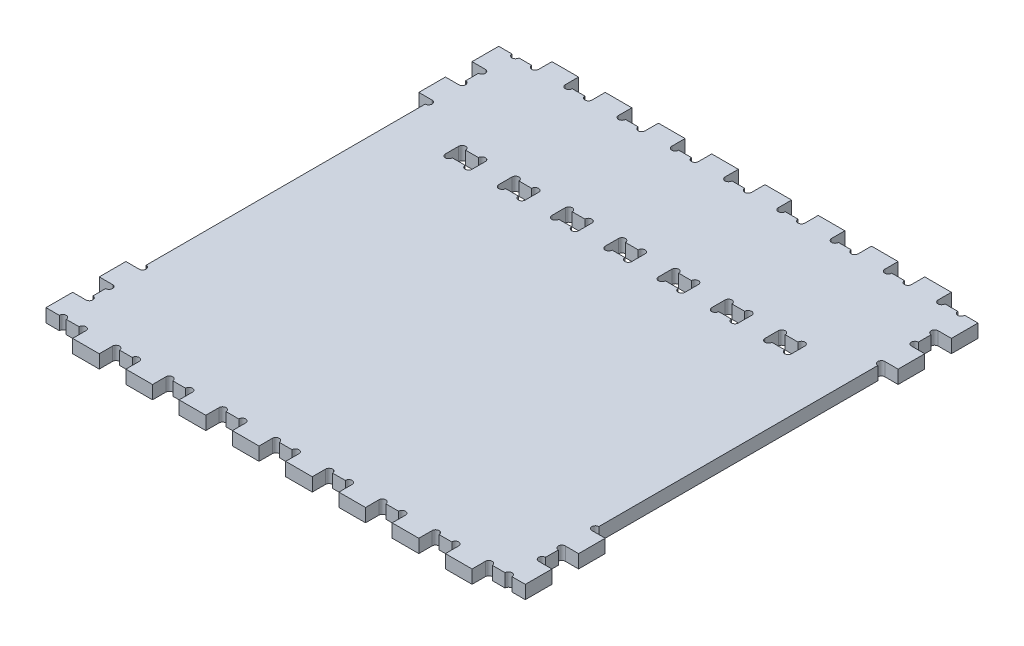
SolidWorks part; units mm, degrees
ref_plane "Front Plane" through (0, 0, 0) normal (0, 0, 1) x (1, 0, 0)
ref_plane "Top Plane" through (0, 0, 0) normal (0, 1, 0) x (1, 0, 0)
ref_plane "Right Plane" through (0, 0, 0) normal (1, 0, 0) x (0, 0, -1)
sketch "Sketch1" plane through (0, 0, 0) normal (0, 1, 0) x (1, 0, 0)
  line L1 (228.6, -228.6) -> (-228.6, -228.6)
  line L2 (228.6, -228.6) -> (228.6, 228.6)
  line L3 (228.6, 228.6) -> (-228.6, 228.6)
  line L4 (-228.6, -228.6) -> (-228.6, 228.6)
  line L5 (228.6, -228.6) -> (-228.6, 228.6) construction
  line L6 (228.6, 228.6) -> (-228.6, -228.6) construction
  point P0 (0, 0)
  dimension "D1" = 457.2
  dimension "D2" = 457.2
extrude "Boss-Extrude1" add sketch "Sketch1" along normal blind 12.7
sketch "Sketch2" plane through (0, 12.7, 0) normal (0, 1, 0) x (1, 0, 0)
  line L0 (228.6, 228.6) -> (-228.6, 228.6) construction
  line L1 (-215.9, 228.6) -> (-190.5, 228.6)
  line L2 (-215.9, 228.6) -> (-215.9, 215.9)
  line L3 (-215.9, 215.9) -> (-190.5, 215.9)
  line L4 (-190.5, 228.6) -> (-190.5, 215.9)
  line L5 (-215.9, 215.9) -> (-228.6, 215.9) construction
  line L6 (-228.6, 228.6) -> (-228.6, -228.6) construction
  circle A0 centre (-212.598, 215.9) radius 3.302
  circle A1 centre (-193.802, 215.9) radius 3.302
  line M8 (228.6, 228.6) -> (-228.6, 228.6)
  dimension "D3" = 6.604
  dimension "D4" = 6.604
  dimension "D1" = 25.4
  dimension "D2" = 12.7
  dimension "D5" = 12.7
extrude "Cut-Extrude1" cut sketch "Sketch2" against normal blind 12.7 contours A1 L4 L2 A0 L3 M8 | L3 A0 | L3 A1 | L3 A1 | L3 A0 region at (-203.2, 12.7, -222.8379) region at (-212.598, 12.7, -217.3014) region at (-212.598, 12.7, -214.4986) region at (-193.802, 12.7, -214.4986) region at (-193.802, 12.7, -217.3014)
pattern_linear "LPattern1" count 9 spacing 50.8 along (1, 0, 0) of "Cut-Extrude1"
ref_plane "Plane1" through (0, 0, 0) normal (0, 0, -1) x (-1, 0, 0)
ref_plane "Plane2" through (0, 0, 0) normal (-1, 0, 0) x (0, 0, 1)
mirror "Mirror1" about plane through (0, 0, 0) normal (0, 0, -1) of "LPattern1"
sketch "Sketch3" plane through (0, 12.7, 0) normal (0, 1, 0) x (1, 0, 0)
  line L1 (-228.6, 228.6) -> (-215.9, 228.6)
  line L2 (-228.6, 228.6) -> (-228.6, 215.9)
  line L3 (-228.6, 215.9) -> (-215.9, 215.9)
  line L4 (-215.9, 228.6) -> (-215.9, 215.9)
extrude "Cut-Extrude2" cut sketch "Sketch3" against normal through all
mirror "Mirror2" about plane through (0, 0, 0) normal (-1, 0, 0) of "Cut-Extrude2"
mirror "Mirror3" about plane through (0, 0, 0) normal (0, 0, -1) of "Mirror2"
sketch "Sketch4" plane through (0, 12.7, 0) normal (0, 1, 0) x (1, 0, 0)
  line L0 (-228.6, 215.9) -> (-228.6, -215.9) construction
  line L1 (-228.6, 190.5) -> (-215.9, 190.5)
  line L2 (-228.6, 190.5) -> (-228.6, 165.1)
  line L3 (-228.6, 165.1) -> (-215.9, 165.1)
  line L4 (-215.9, 190.5) -> (-215.9, 165.1)
  line L5 (-215.9, 190.5) -> (-186.3664, 190.5) construction
  line L6 (-186.3664, 190.5) -> (-186.3664, 228.6) construction
  line L7 (-165.1, 228.6) -> (-190.5, 228.6) construction
  circle A0 centre (-215.9, 187.198) radius 3.302
  circle A1 centre (-215.9, 168.402) radius 3.302
  dimension "D3" = 6.604
  dimension "D4" = 6.604
  dimension "D1" = 12.7
  dimension "D2" = 25.4
  dimension "D5" = 38.1
extrude "Cut-Extrude3" cut sketch "Sketch4" against normal through all contours A1 L4 A0 L1 L2 L3 | L4 A0 | L4 A1 | L4 A1 | L4 A0 region at (-222.8379, 12.7, -177.8) region at (-214.4986, 12.7, -187.198) region at (-217.3014, 12.7, -187.198) region at (-217.3014, 12.7, -168.402) region at (-214.4986, 12.7, -168.402)
pattern_linear "LPattern2" count 9 spacing 50.8 along (0, 0, 1) of "Cut-Extrude3"
mirror "Mirror4" about plane through (0, 0, 0) normal (-1, 0, 0) of "LPattern2"
sketch "Sketch5" plane through (0, 12.7, 0) normal (0, 1, 0) x (1, 0, 0)
  line L0 (-165.1, 114.3) -> (-165.1, 215.9) construction
  line L1 (-158.496, 114.3) -> (-146.304, 114.3)
  line L2 (-165.1, 114.3) -> (-165.1, 101.6)
  line L3 (-158.496, 101.6) -> (-146.304, 101.6)
  line L4 (-139.7, 114.3) -> (-139.7, 101.6)
  arc A0 (-158.496, 114.3) -> (-165.1, 114.3) centre (-161.798, 114.3) ccw
  arc A1 (-139.7, 114.3) -> (-146.304, 114.3) centre (-143.002, 114.3) ccw
  arc A2 (-146.304, 101.6) -> (-139.7, 101.6) centre (-143.002, 101.6) ccw
  arc A3 (-165.1, 101.6) -> (-158.496, 101.6) centre (-161.798, 101.6) ccw
  dimension "D3" = 6.604
  dimension "D1" = 25.4
  dimension "D2" = 12.7
  dimension "D4" = 101.6
extrude "Cut-Extrude4" cut sketch "Sketch5" against normal through all
pattern_linear "LPattern3" count 7 spacing 50.8 along (1, 0, 0) of "Cut-Extrude4"
sketch "Sketch6" plane through (0, 12.7, 0) normal (0, 1, 0) x (1, 0, 0)
  line L1 (-228.6, 139.7) -> (-215.9, 139.7)
  line L2 (-228.6, 139.7) -> (-228.6, -139.7)
  line L3 (-228.6, -139.7) -> (-215.9, -139.7)
  line L4 (-215.9, 139.7) -> (-215.9, -139.7)
  line L5 (228.6, 139.7) -> (215.9, 139.7)
  line L6 (228.6, 139.7) -> (228.6, -139.7)
  line L7 (228.6, -139.7) -> (215.9, -139.7)
  line L8 (215.9, 139.7) -> (215.9, -139.7)
extrude "Cut-Extrude5" cut sketch "Sketch6" against normal through all
sketch "Sketch7" plane through (0, 12.7, 0) normal (0, 1, 0) x (1, 0, 0)
  line L0 (-215.9, 133.096) -> (-215.9, 120.904) construction
  line L1 (-215.9, 133.096) -> (-208.346, 133.096)
  line L2 (-215.9, 133.096) -> (-215.9, -130.6902)
  line L3 (-215.9, -130.6902) -> (-208.346, -130.6902)
  line L4 (-208.346, 133.096) -> (-208.346, -130.6902)
  line L5 (215.9, 133.096) -> (215.9, 120.904) construction
  line L6 (215.9, 133.096) -> (210.1226, 133.096)
  line L7 (215.9, 133.096) -> (215.9, -128.0701)
  line L8 (215.9, -128.0701) -> (210.1226, -128.0701)
  line L9 (210.1226, 133.096) -> (210.1226, -128.0701)
  arc A0 (-215.9, 133.096) -> (-215.9, 139.7) centre (-215.9, 136.398) ccw construction
extrude "Boss-Extrude2" add sketch "Sketch7" against normal blind 12.7
